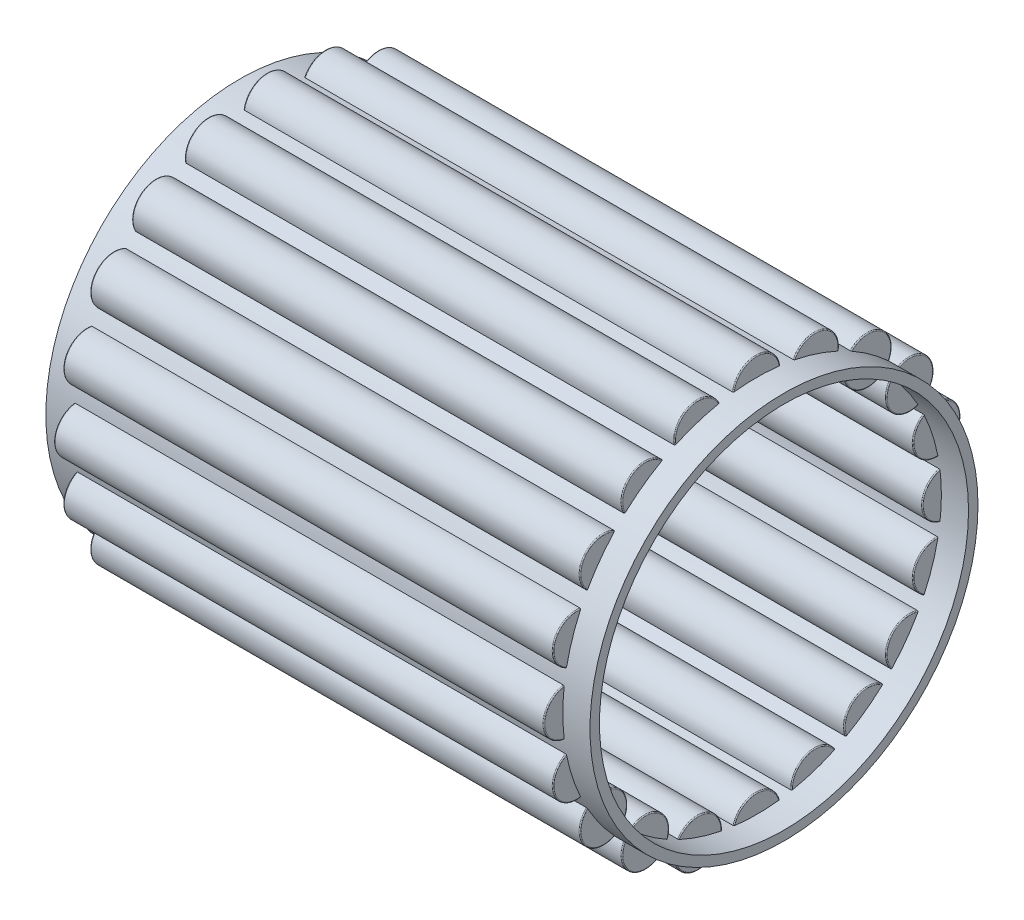
SolidWorks part; units mm, degrees
ref_plane "Plane1" through (0, 0, 0) normal (0, 0, 1) x (1, 0, 0)
ref_plane "Plane2" through (0, 0, 0) normal (0, 1, 0) x (1, 0, 0)
ref_plane "Plane3" through (0, 0, 0) normal (1, 0, 0) x (0, 0, -1)
sketch "Clipboard" plane through (0, 0, 0) normal (0, 0, 1) x (1, 0, 0)
  line L0 (-10, 0) -> (10, 0) construction
  line L1 (-21, -0.7333) -> (0.0122, -8.3811)
  line L2 (-21, -0.7333) -> (-4.0855, 5.423)
  line L3 (-21, -0.7333) -> (-13, -3.6451)
  line L4 (-21, -0.7333) -> (-35, -1.2222)
  dimension "OD" = 18
  dimension "Count" = 20
  dimension "Show_count" = 20
  dimension "Max_count" = 20
  dimension "Min_count" = 2
  dimension "RollCLRad" = 8
  dimension "Bore" = 14
sketch "CagSpiSke" plane through (0, 0, 0) normal (0, 0, 1) x (1, 0, 0)
  line L0 (11.5, 7.8) -> (11.5, 8.2)
  line L1 (11.5, 8.2) -> (-11.5, 8.2)
  line L2 (-11.5, 8.2) -> (-11.5, 7.8)
  line L3 (-11.5, 7.8) -> (11.5, 7.8)
  line L4 (-12.7, 0) -> (12.7, 0) construction
  dimension "cagRadius" = 7.8
  dimension "thickness" = 0.4
  dimension "Width" = 23
  dimension "halfWidth" = 11.5
revolve "CageSpine" add sketch "CagSpiSke" angle 360 about L4 reverse direction yes
sketch "RolDetSke" plane through (0, 0, 0) normal (0, 0, 1) x (1, 0, 0)
  line L0 (-17.78, 8) -> (17.78, 8) construction
  line L2 (-10.31, 9) -> (10.31, 9)
  line L3 (-10.35, 8.96) -> (-10.35, 8)
  line L5 (-10.35, 8) -> (10.35, 8)
  line L6 (10.35, 8.96) -> (10.35, 8)
  arc A0 (-10.31, 9) -> (-10.35, 8.96) centre (-10.31, 8.96) ccw
  arc A1 (10.35, 8.96) -> (10.31, 9) centre (10.31, 8.96) ccw
  dimension "radius" = 0.04
  dimension "Roller_diameter" = 2
  dimension "Cyl_Len" = 20.7
  dimension "CLRad" = 8
  dimension "halfCylLen" = 10.35
revolve "RollerDetailed" add sketch "RolDetSke" angle 360 about L0 reverse direction yes
ref_axis "Axis1" through (-50, 0, 0) along (1, 0, 0)
pattern_circular "RollersDetailed" count 20 every 18 about axis through (-50, 0, 0) along (1, 0, 0) of "RollerDetailed"
sketch "RolSimSke" plane through (0, 0, 0) normal (0, 0, 1) x (1, 0, 0)
  line L0 (-17.78, 0) -> (17.78, 0) construction
  line L1 (-12.7, 0) -> (-38.1, 0) construction
  line L3 (-10.31, 9) -> (10.31, 9)
  line L4 (-10.35, 8.96) -> (-10.35, 7.04)
  line L5 (-10.31, 7) -> (10.31, 7)
  line L6 (10.35, 8.96) -> (10.35, 7.04)
  arc A0 (10.35, 7.04) -> (10.31, 7) centre (10.31, 7.04) cw
  arc A1 (10.31, 9) -> (10.35, 8.96) centre (10.31, 8.96) cw
  arc A2 (-10.35, 8.96) -> (-10.31, 9) centre (-10.31, 8.96) cw
  arc A3 (-10.31, 7) -> (-10.35, 7.04) centre (-10.31, 7.04) cw
  point P13 (10.35, 9)
  point P16 (-10.35, 9)
  point P19 (-10.35, 7)
  dimension "radius" = 0.04
  dimension "D1" = 10.35
  dimension "Cyl_Len" = 20.7
  dimension "Bore" = 14
  dimension "Roller_diameter" = 2
revolve "RollersSimplified" [suppressed] add sketch "RolSimSke" angle 360 about L0
equation "\"RollCLRad@Clipboard\" = ( \"OD@Clipboard\" + \"Bore@Clipboard\" )  / 4"
equation "\"CLRad@RolDetSke\" = \"RollCLRad@Clipboard\""
equation "\"thickness@CagSpiSke\"  = ( \"OD@Clipboard\" - \"Bore@Clipboard\" )  / 10"
equation "\"cagRadius@CagSpiSke\" =  \"RollCLRad@Clipboard\" -  ( \"thickness@CagSpiSke\" / 2 ) "
equation "\"halfWidth@CagSpiSke\" = \"Width@CagSpiSke\" / 2"
equation "\"Bore@RolSimSke\" = \"Bore@Clipboard\""
equation "\"Roller_diameter@RolDetSke\" =  ( \"OD@Clipboard\" - \"Bore@Clipboard\" )  / 2"
equation "\"halfCylLen@RolDetSke\" = \"Cyl_Len@RolDetSke\" / 2"
equation "\"radius@RolDetSke\" = \"Roller_diameter@RolDetSke\" / 50"
equation "\"Cyl_Len@RolSimSke\" = \"Cyl_Len@RolDetSke\""
equation "\"D1@RolSimSke\" = \"Cyl_Len@RolSimSke\"/2"
equation "\"radius@RolSimSke\" = \"radius@RolDetSke\""
equation "\"Roller_diameter@RolSimSke\" =  ( \"OD@Clipboard\" - \"Bore@Clipboard\" )  / 2"
equation "\"Max_count@Clipboard\" = int( 3.14159265 / atn(( \"Roller_diameter@RolDetSke\" / 2) / sqr(\"RollCLRad@Clipboard\"  * \"RollCLRad@Clipboard\" - ( \"Roller_diameter@RolDetSke\" / 2) *  ( \"Roller_diameter@RolDetSke\" / 2))))"
equation "\"Max_count@Clipboard\" = ((sgn( \"Max_count@Clipboard\" - \"Count@Clipboard\" )-1)*( \"Max_count@Clipboard\" - \"Count@Clipboard\" ))/-2+ \"Count@Clipboard\""
equation "\"Count@RollersDetailed\" = int( \"Show_count@Clipboard\" ) "
equation "\"Count@RollersDetailed\" = ((sgn( \"Count@RollersDetailed\" - \"Max_count@Clipboard\" )-1)*( \"Count@RollersDetailed\" - \"Max_count@Clipboard\" ))/-2+ \"Max_count@Clipboard\""
equation "\"Count@RollersDetailed\" = ((sgn( \"Count@RollersDetailed\" - \"Min_count@Clipboard\" )+1)*( \"Count@RollersDetailed\" - \"Min_count@Clipboard\"))/2 +\"Min_count@Clipboard\""
equation "\"Angle@RollersDetailed\" = 360.0 / \"Max_count@Clipboard\""
